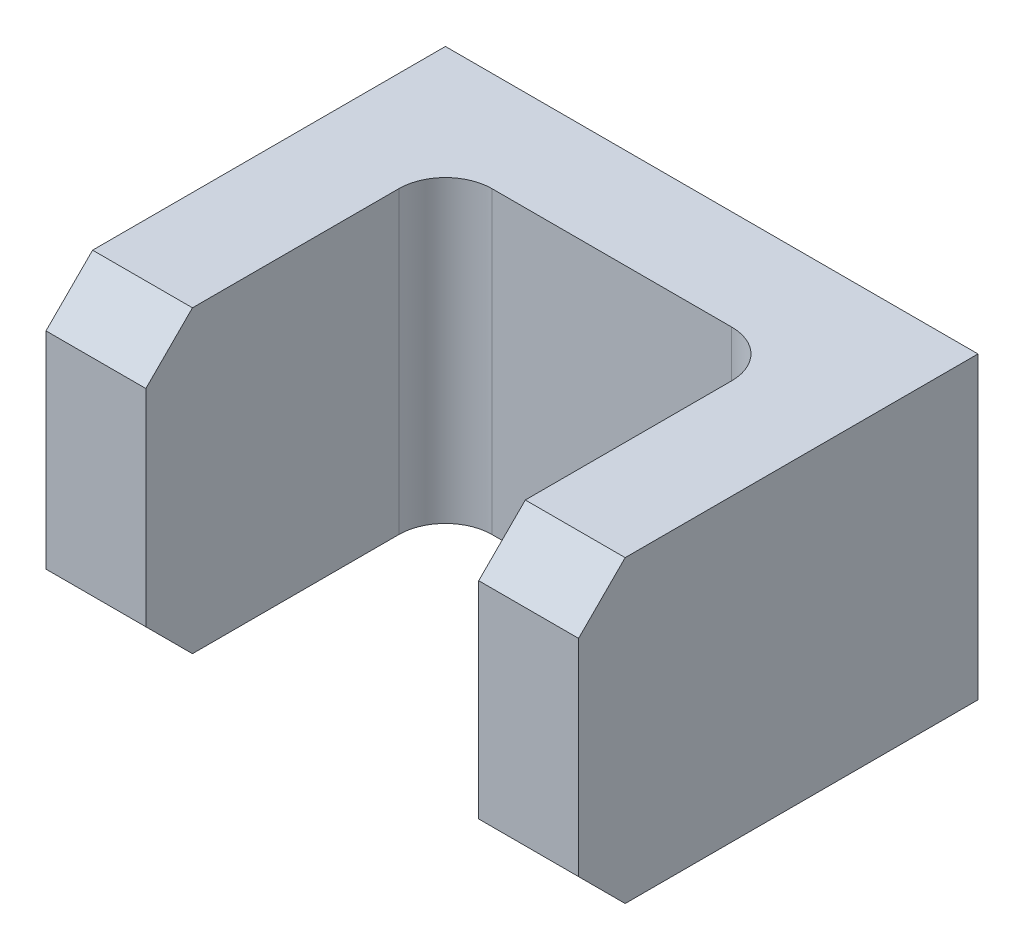
SolidWorks part; units mm, degrees
ref_plane "Front Plane" through (0, 0, 0) normal (0, 0, 1) x (1, 0, 0)
ref_plane "Top Plane" through (0, 0, 0) normal (0, 1, 0) x (1, 0, 0)
ref_plane "Right Plane" through (0, 0, 0) normal (1, 0, 0) x (0, 0, -1)
sketch "Sketch3" plane through (0, 0, 0) normal (1, 0, 0) x (0, 0, -1)
  line L0 (-30, -15.5) -> (-23, -22.5)
  line L1 (30, 22.5) -> (-23, 22.5)
  line L2 (30, 22.5) -> (30, -22.5)
  line L3 (30, -22.5) -> (-23, -22.5)
  line L4 (-30, 15.5) -> (-30, -15.5)
  line L5 (0, -22.5) -> (0, 22.5) construction
  line L6 (30, 0) -> (-30, 0) construction
  line L7 (-23, 22.5) -> (-30, 15.5)
  point P0 (0, 0)
  point P1 (-30, -22.5)
  point P80 (-30, 22.5)
  dimension "D1" = 45
  dimension "D2" = 60
extrude "Boss-Extrude1" add sketch "Sketch3" along normal blind 40 and the other way blind 40
sketch "Sketch4" plane through (0, 22.5, 0) normal (0, 1, 0) x (1, 0, 0)
  line L0 (0, 0) -> (0, -32.0269) construction
  line L1 (-40, -30) -> (40, -30) construction
  line L2 (18, 15) -> (-18, 15)
  line L3 (25, 8) -> (25, -30)
  line L4 (25, -30) -> (-25, -30)
  line L5 (-25, 8) -> (-25, -30)
  line L6 (0, -30) -> (0, 15) construction
  line L7 (25, -11) -> (-25, -11) construction
  arc A0 (18, 15) -> (25, 8) centre (18, 8) cw
  arc A1 (-25, 8) -> (-18, 15) centre (-18, 8) cw
  point P3 (0, -11)
  point P13 (25, 15)
  point P16 (-25, 15)
  dimension "D4" = 7
  dimension "D1" = 0
  dimension "D2" = 50
  dimension "D3" = 45
extrude "Cut-Extrude1" cut sketch "Sketch4" against normal through all and the other way through all
